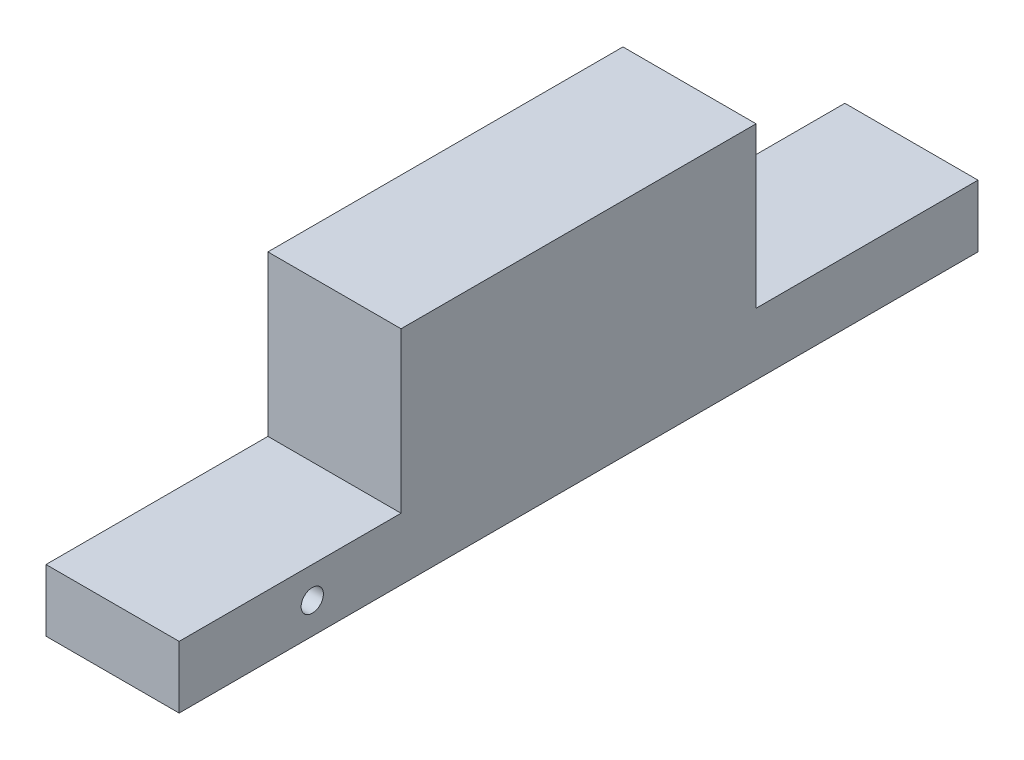
SolidWorks part; units mm, degrees
ref_plane "xy_plane" through (0, 0, 0) normal (0, 0, 1) x (1, 0, 0)
ref_plane "zx_plane" through (0, 0, 0) normal (0, 1, 0) x (1, 0, 0)
ref_plane "yz_plane" through (0, 0, 0) normal (1, 0, 0) x (0, 0, -1)
ref_axis "x_axis" through (-80.9, 0, 0) along (1, 0, 0)
ref_axis "y_axis" through (0, -50, 0) along (0, 1, 0)
ref_axis "z_axis" through (0, 0, -80.9) along (0, 0, 1)
ref_plane "xMid_plane" through (0, 0, 0) normal (1, 0, 0) x (0, 0, -1)
ref_plane "xMin_plane" through (-15, 0, 0) normal (1, 0, 0) x (0, 0, -1)
ref_plane "xMax_plane" through (15, 0, 0) normal (1, 0, 0) x (0, 0, -1)
ref_plane "yMid_plane" through (0, 0, 0) normal (0, 1, 0) x (1, 0, 0)
ref_plane "yMin_plane" through (0, -25, 0) normal (0, 1, 0) x (1, 0, 0)
ref_plane "yMax_plane" through (0, 25, 0) normal (0, 1, 0) x (1, 0, 0)
ref_plane "zMid_plane" through (0, 0, 0) normal (0, 0, 1) x (1, 0, 0)
ref_plane "zMin_plane" through (0, 0, -90) normal (0, 0, 1) x (1, 0, 0)
ref_plane "zMax_plane" through (0, 0, 90) normal (0, 0, 1) x (1, 0, 0)
sketch "projectionYz_sketch" plane through (0, 0, 0) normal (1, 0, 0) x (0, 0, -1)
  line L0 (90, -25) -> (90, -11)
  line L1 (90, -11) -> (40, -11)
  line L2 (40, -11) -> (40, 25)
  line L3 (40, 25) -> (-40, 25)
  line L4 (-40, 25) -> (-40, -11)
  line L5 (-40, -11) -> (-90, -11)
  line L6 (-90, -11) -> (-90, -25)
  line L7 (90, -25) -> (-90, -25)
  line L8 (90, 55) -> (90, -55) construction
  line L9 (55, -25) -> (-55, -25) construction
  line L10 (-90, 55) -> (-90, -55) construction
  line L11 (40, 80) -> (40, -30) construction
  line L12 (-40, 80) -> (-40, -30) construction
  line L13 (55, 25) -> (-55, 25) construction
  dimension "D1" = 14
extrude "mainBody_extrude" add sketch "projectionYz_sketch" along normal up to surface (15 mm away) from surface up to plane "xMax_plane" starting at plane "xMin_plane"
sketch "pivotShaftHole_sketch" plane through (0, 0, 0) normal (1, 0, 0) x (0, 0, -1)
  circle A0 centre (-60, -18) radius 2.51
  dimension "D1" = 5.02
extrude "pivotShaftHole_cut" cut sketch "pivotShaftHole_sketch" against normal through all both and the other way through all from surface starting at plane "xMid_plane"
sketch "springAnchorHole_sketch" plane through (0, 0, 0) normal (1, 0, 0) x (0, 0, -1)
  line L0 (-51.6759, -14.578) -> (-60.6759, -14.578) construction
  line L1 (80.9, 0) -> (-80.9, 0) construction
  circle A0 centre (-51.6759, -14.578) radius 1
  dimension "D2" = 2
  dimension "D3" = 9
equation "\"D1@xMin_plane\" = \"externalParameters.this.extent.x\" / 2"
equation "\"D1@xMax_plane\" = \"externalParameters.this.extent.x\" / 2"
equation "\"D1@yMin_plane\" = \"externalParameters.this.extent.y\" / 2"
equation "\"D1@yMax_plane\"= \"externalParameters.this.extent.y\" / 2"
equation "\"D1@zMin_plane\" = \"externalParameters.this.extent.z\" / 2"
equation "\"D1@zMax_plane\" = \"externalParameters.this.extent.z\" / 2"
equation "\"D1@projectionYz_sketch\" = \"externalParameters.this.foot.extent.y\""
equation "\"D1@pivotShaftHole_sketch\"=\"externalParameters.pivotShaft.holeDiameter\""
equation "\"D2@springAnchorHole_sketch\" = \"externalParameters.this.springAnchorHole.diameter\""
equation "\"D3@springAnchorHole_sketch\"=\"externalParameters.this.springAnchorOffset\""
